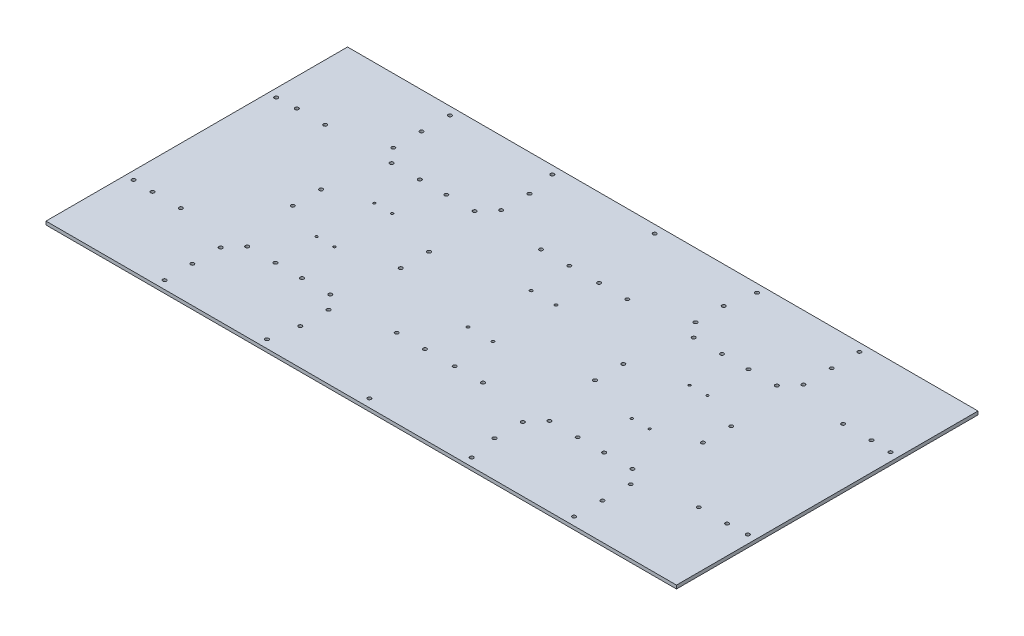
SolidWorks part; units mm, degrees
ref_plane "Front Plane" through (0, 0, 0) normal (0, 0, 1) x (1, 0, 0)
ref_plane "Top Plane" through (0, 0, 0) normal (0, 1, 0) x (1, 0, 0)
ref_plane "Right Plane" through (0, 0, 0) normal (1, 0, 0) x (0, 0, -1)
sketch "Sketch1" plane through (0, 0, 0) normal (0, 1, 0) x (1, 0, 0)
  line L0 (0, 139.7) -> (0, -139.7) construction
  line L1 (-292.1, 139.7) -> (292.1, 139.7)
  line L2 (-292.1, 139.7) -> (-292.1, -139.7)
  line L3 (-292.1, -139.7) -> (292.1, -139.7)
  line L4 (292.1, 139.7) -> (292.1, -139.7)
  line L5 (-292.1, 139.7) -> (292.1, -139.7) construction
  line L6 (-292.1, -139.7) -> (292.1, 139.7) construction
  line L7 (-284.6, 132.2) -> (284.6, 132.2) construction
  line L8 (-284.6, 132.2) -> (-284.6, -132.2) construction
  line L9 (-284.6, -132.2) -> (284.6, -132.2) construction
  line L10 (284.6, 132.2) -> (284.6, -132.2) construction
  line L11 (-284.6, 132.2) -> (284.6, -132.2) construction
  line L12 (-284.6, -132.2) -> (284.6, 132.2) construction
  line L13 (-292.1, 0) -> (292.1, 0) construction
  line L14 (284.6, 132.2) -> (284.6, -132.2) construction
  circle A0 centre (-284.6, 66.1) radius 1.65
  circle A1 centre (-189.7333, 132.2) radius 1.65
  circle A2 centre (-94.8667, 132.2) radius 1.65
  circle A3 centre (-284.6, -66.1) radius 1.65
  circle A4 centre (-94.8667, -132.2) radius 1.65
  circle A5 centre (-189.7333, -132.2) radius 1.65
  circle A6 centre (189.7333, -132.2) radius 1.65
  circle A7 centre (94.8667, -132.2) radius 1.65
  circle A8 centre (94.8667, 132.2) radius 1.65
  circle A9 centre (189.7333, 132.2) radius 1.65
  circle A10 centre (284.6, -66.1) radius 1.65
  circle A11 centre (284.6, 66.1) radius 1.65
  circle A12 centre (0, 132.2) radius 1.65
  circle A13 centre (0, -132.2) radius 1.65
  point P0 (0, 0)
  point P6 (0, 0)
  dimension "D5" = 3.3
  dimension "D6" = 3.3
  dimension "D7" = 3.3
  dimension "D12" = 3.3
  dimension "D13" = 3.3
  dimension "D1" = 584.2
  dimension "D2" = 279.4
  dimension "D3" = 7.5
  dimension "D4" = 7.5
  dimension "D8" = 66.1
  dimension "D9" = 94.8667
  dimension "D10" = 94.8667
  dimension "D11" = 94.8667
extrude "Boss-Extrude1" add sketch "Sketch1" along normal blind 3.175
sketch "Sketch2" plane through (0, 3.175, 0) normal (0, 1, 0) x (1, 0, 0)
  line L0 (0, 139.7) -> (0, -139.7) construction
  line L1 (292.1, 139.7) -> (-292.1, 139.7) construction
  line L2 (-292.1, -139.7) -> (292.1, -139.7) construction
  line L3 (-140, 139.7) -> (-140, -139.7) construction
  line L5 (-292.1, 0) -> (292.1, 0) construction
  line L6 (-292.1, 139.7) -> (-292.1, -139.7) construction
  line L7 (292.1, -139.7) -> (292.1, 139.7) construction
  line L8 (-190, 139.7) -> (-190, -139.7) construction
  circle A0 centre (-190, 13.1) radius 1.65
  circle A6 centre (-266.2, 66.8739) radius 1.65
  circle A7 centre (-240, 66.8739) radius 1.65
  circle A8 centre (-178.5, 66.8739) radius 1.65
  circle A9 centre (-152.3, 66.8739) radius 1.65
  circle A10 centre (-190, 106.2) radius 1.65
  circle A11 centre (-190, 80) radius 1.65
  circle A12 centre (-190, -80) radius 1.65
  circle A13 centre (-190, -106.2) radius 1.65
  circle A14 centre (-152.3, -66.8739) radius 1.65
  circle A15 centre (-178.5, -66.8739) radius 1.65
  circle A16 centre (-240, -66.8739) radius 1.65
  circle A17 centre (-266.2, -66.8739) radius 1.65
  circle A18 centre (-190, -13.1) radius 1.65
  circle A19 centre (-90, -13.1) radius 1.65
  circle A20 centre (-13.8, -66.8739) radius 1.65
  circle A21 centre (-40, -66.8739) radius 1.65
  circle A22 centre (-101.5, -66.8739) radius 1.65
  circle A23 centre (-127.7, -66.8739) radius 1.65
  circle A24 centre (-90, -106.2) radius 1.65
  circle A25 centre (-90, -80) radius 1.65
  circle A26 centre (-90, 80) radius 1.65
  circle A27 centre (-90, 106.2) radius 1.65
  circle A28 centre (-127.7, 66.8739) radius 1.65
  circle A29 centre (-101.5, 66.8739) radius 1.65
  circle A30 centre (-40, 66.8739) radius 1.65
  circle A31 centre (-13.8, 66.8739) radius 1.65
  circle A32 centre (-90, 13.1) radius 1.65
  circle A33 centre (90, 13.1) radius 1.65
  circle A34 centre (13.8, 66.8739) radius 1.65
  circle A35 centre (40, 66.8739) radius 1.65
  circle A36 centre (101.5, 66.8739) radius 1.65
  circle A37 centre (127.7, 66.8739) radius 1.65
  circle A38 centre (90, 106.2) radius 1.65
  circle A39 centre (90, 80) radius 1.65
  circle A40 centre (90, -80) radius 1.65
  circle A41 centre (90, -106.2) radius 1.65
  circle A42 centre (127.7, -66.8739) radius 1.65
  circle A43 centre (101.5, -66.8739) radius 1.65
  circle A44 centre (40, -66.8739) radius 1.65
  circle A45 centre (13.8, -66.8739) radius 1.65
  circle A46 centre (90, -13.1) radius 1.65
  circle A47 centre (190, -13.1) radius 1.65
  circle A48 centre (266.2, -66.8739) radius 1.65
  circle A49 centre (240, -66.8739) radius 1.65
  circle A50 centre (178.5, -66.8739) radius 1.65
  circle A51 centre (152.3, -66.8739) radius 1.65
  circle A52 centre (190, -106.2) radius 1.65
  circle A53 centre (190, -80) radius 1.65
  circle A54 centre (190, 80) radius 1.65
  circle A55 centre (190, 106.2) radius 1.65
  circle A56 centre (152.3, 66.8739) radius 1.65
  circle A57 centre (178.5, 66.8739) radius 1.65
  circle A58 centre (240, 66.8739) radius 1.65
  circle A59 centre (266.2, 66.8739) radius 1.65
  circle A60 centre (190, 13.1) radius 1.65
  dimension "D6" = 3.3
  dimension "D4" = 13.1
  dimension "D10" = 26.2
  dimension "D11" = 26.2
  dimension "D14" = 26.2
  dimension "D15" = 11.5
  dimension "D3" = 190
  dimension "D16" = 50
  dimension "D17" = 80
  dimension "D18" = 50
  dimension "D19" = 66.8739
extrude "Cut-Extrude1" cut sketch "Sketch2" against normal up to surface (3.175 mm away) up to face at (0, 0, 0)
sketch "Sketch3" plane through (0, 3.175, 0) normal (0, 1, 0) x (1, 0, 0)
  line L1 (-11.525, 29.25) -> (11.525, 29.25) construction
  line L2 (-11.525, 29.25) -> (-11.525, -29.25) construction
  line L3 (-11.525, -29.25) -> (11.525, -29.25) construction
  line L4 (11.525, 29.25) -> (11.525, -29.25) construction
  line L5 (-11.525, 29.25) -> (11.525, -29.25) construction
  line L6 (-11.525, -29.25) -> (11.525, 29.25) construction
  line L7 (-146.05, 139.7) -> (-146.05, -139.7) construction
  line L8 (292.1, 139.7) -> (-292.1, 139.7) construction
  line L9 (-292.1, -139.7) -> (292.1, -139.7) construction
  line L10 (0, 139.7) -> (0, -139.7) construction
  line L11 (-292.1, 139.7) -> (-292.1, -139.7) construction
  line L12 (154.3, -26.75) -> (137.8, 26.75) construction
  line L13 (-154.3, 26.75) -> (-137.8, 26.75) construction
  line L14 (-154.3, 26.75) -> (-154.3, -26.75) construction
  line L15 (-154.3, -26.75) -> (-137.8, -26.75) construction
  line L16 (-137.8, 26.75) -> (-137.8, -26.75) construction
  line L17 (-154.3, 26.75) -> (-137.8, -26.75) construction
  line L18 (-154.3, -26.75) -> (-137.8, 26.75) construction
  line L19 (154.3, 26.75) -> (137.8, -26.75) construction
  line L20 (137.8, 26.75) -> (137.8, -26.75) construction
  line L21 (154.3, -26.75) -> (137.8, -26.75) construction
  line L22 (154.3, 26.75) -> (154.3, -26.75) construction
  line L23 (154.3, 26.75) -> (137.8, 26.75) construction
  line L24 (146.05, 139.7) -> (146.05, -139.7) construction
  circle A0 centre (-11.525, 29.25) radius 1.3
  circle A1 centre (11.525, 29.25) radius 1.3
  circle A2 centre (11.525, -29.25) radius 1.3
  circle A3 centre (-11.525, -29.25) radius 1.3
  circle A4 centre (-154.3, 26.75) radius 1.1
  circle A5 centre (-137.8, 26.75) radius 1.1
  circle A6 centre (-137.8, -26.75) radius 1.1
  circle A7 centre (-154.3, -26.75) radius 1.1
  circle A8 centre (154.3, -26.75) radius 1.1
  circle A9 centre (137.8, -26.75) radius 1.1
  circle A10 centre (137.8, 26.75) radius 1.1
  circle A11 centre (154.3, 26.75) radius 1.1
  point P0 (0, 0)
  point P20 (-146.05, 0)
  point P39 (146.05, 0)
  dimension "D1" = 2.6
  dimension "D6" = 2.2
  dimension "D2" = 58.5
  dimension "D3" = 23.05
  dimension "D4" = 292.1
  dimension "D5" = 146.05
  dimension "D7" = 53.5
  dimension "D8" = 16.5
extrude "Cut-Extrude2" cut sketch "Sketch3" against normal up to surface (3.175 mm away) up to face at (-101.5, 0, 68.5239)
equation "\"D6@Sketch1\"=\"D5@Sketch1\""
equation "\"D7@Sketch1\"=\"D5@Sketch1\""
equation "\"D10@Sketch1\"=\"D9@Sketch1\""
equation "\"D12@Sketch1\"=\"D5@Sketch1\""
equation "\"D13@Sketch1\"=\"D5@Sketch1\""
equation "\"D11@Sketch2\"=\"D10@Sketch2\""
equation "\"D4@Sketch2\"=\"D10@Sketch2\"/2"
equation "\"D14@Sketch2\"=\"D10@Sketch2\""
equation "\"D5@Sketch3\"=\"D4@Sketch3\"/2"
